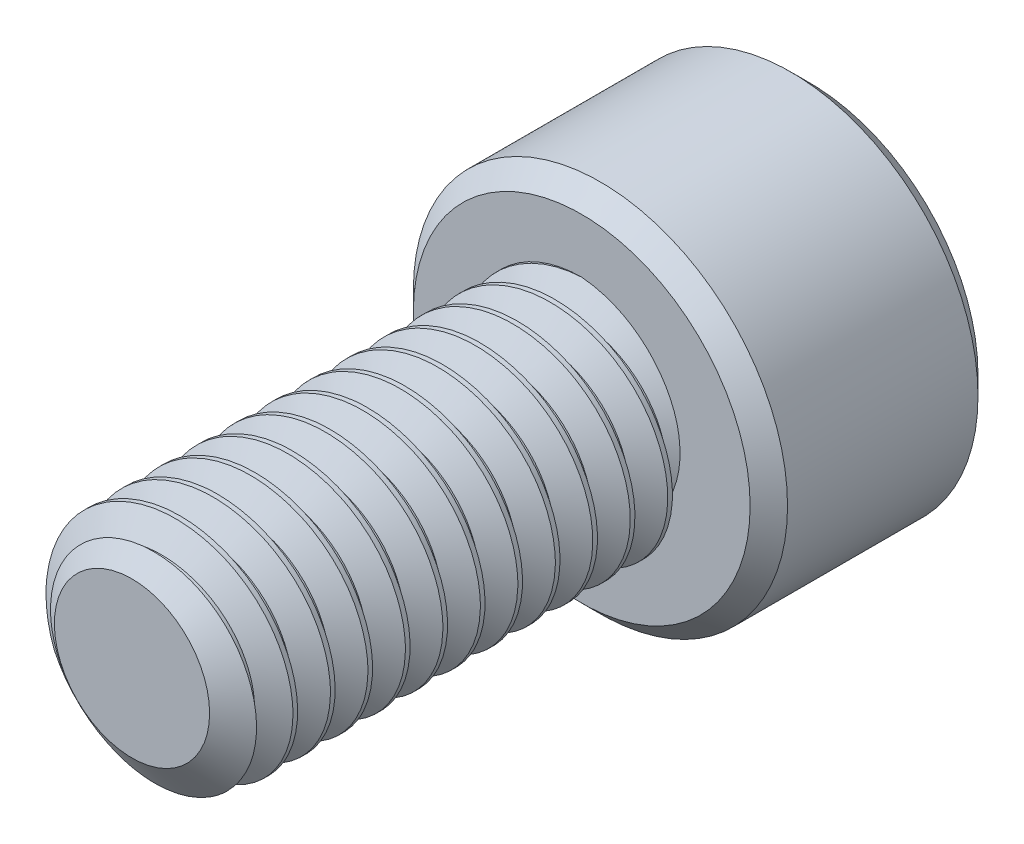
SolidWorks part; units mm, degrees
note: '?' marks a value the reader was unsure of.
other "DetailItem1"
material "Nylon 6/10"
ref_plane "Front Plane" through (0, 0, 0) normal (0, 0, 1) x (1, 0, 0)
ref_plane "Top Plane" through (0, 0, 0) normal (0, 1, 0) x (1, 0, 0)
ref_plane "Right Plane" through (0, 0, 0) normal (1, 0, 0) x (0, 0, -1)
sketch "Sketch1" plane through (0, 0, 0) normal (0, 0, 1) x (1, 0, 0)
  circle A0 centre (0, 0) radius 2.413
  dimension "OD" = 4.826
extrude "Extrude1" add sketch "Sketch1" against normal blind 9.525
sketch "Sketch2" plane through (0, 0, 0) normal (0, 0, 1) x (1, 0, 0)
  circle A0 centre (0, 0) radius 2.413 construction
  circle A1 centre (0, 0) radius 2.413
curve "Helix/Spiral1" pitch 0.7937 height 10.3187 turns 13 parameters "pitch"=0.7937
sketch "Sketch3" plane through (0, 0, 0) normal (1, 0, 0) x (0, 0, -1)
  line L0 (-0.6945, 2.413) -> (-0.3969, 1.8974)
  line L1 (-0.3969, 1.8974) -> (-0.2977, 1.8974)
  line L2 (-0.2977, 1.8974) -> (0, 2.413)
  line L3 (-0.6945, 2.413) -> (0, 2.413)
  line L4 (-0.3473, 2.413) -> (-0.3473, 1.8974) construction
  line L5 (-0.5457, 2.1552) -> (-0.1488, 2.1552) construction
  line L6 (0, 2.413) -> (0, -2.413) construction
  dimension "D1" = 0.0992
  dimension "D2" = 0.3969
  dimension "D3" = 60
sweep "Cut-Sweep1" cut profiles "Sketch3" path "Helix/Spiral1"
sketch "Sketch4" plane through (0, 0, 0) normal (1, 0, 0) x (0, 0, -1)
  line L0 (0.5388, 2.413) -> (0, 1.6434)
  line L1 (0, 1.6434) -> (0, 2.413)
  line L2 (0.5388, 2.413) -> (0, 2.413)
  line L3 (-0.6945, 2.413) -> (0, 2.413) construction
  line L4 (0, 0) -> (7.0209, 0) construction
  dimension "D1" = 55
  dimension "D2" = 0.254
revolve "Cut-Revolve1" cut sketch "Sketch4" angle 360 about L4
sketch "Sketch6" plane through (0, 0, -9.525) normal (0, 0, -1) x (-1, 0, 0)
  circle A0 centre (0, 0) radius 3.9624
  dimension "head dia" = 7.9248
extrude "Extrude2" add sketch "Sketch6" along normal blind 4.826
sketch "Sketch7" plane through (0, 0, -14.351) normal (0, 0, -1) x (-1, 0, 0)
  line L1 (0, 2.2914) -> (-1.9844, 1.1457)
  line L2 (-1.9844, 1.1457) -> (-1.9844, -1.1457)
  line L3 (-1.9844, -1.1457) -> (0, -2.2914)
  line L4 (0, -2.2914) -> (1.9844, -1.1457)
  line L5 (1.9844, -1.1457) -> (1.9844, 1.1457)
  line L6 (1.9844, 1.1457) -> (0, 2.2914)
  circle A0 centre (0, 0) radius 1.9844 construction
  dimension "hex dia" = 3.9688
extrude "Cut-Extrude1" cut sketch "Sketch7" against normal blind 2.9766
sketch "Sketch8" plane through (0, 0, -14.351) normal (0, 0, -1) x (-1, 0, 0)
  circle A0 centre (0, 0) radius 2.2914
extrude "Cut-Extrude2" cut sketch "Sketch8" against normal through all draft 45
chamfer "Chamfer1" distance 0.3962 angle 45 2 edges at (-3.9624, 0, -14.351) (-3.9624, 0, -9.525)
sketch "Sketch10" plane through (0, 0, -9.525) normal (0, 0, 1) x (1, 0, 0)
  circle A1 centre (0, 0) radius 2.413
  circle A2 centre (0, 0) radius 2.413
  dimension "D1" = 0
ref_plane "Plane1" through (0, 0, -38.1) normal (0, 0, 1) x (1, 0, 0)
extrude "partial thread" [suppressed] add sketch "Sketch10" along normal up to surface (12.7 mm away) separate body
chamfer "Chamfer2" [suppressed] distance 0.0965 angle 45
combine bodies "Combine1" [suppressed] operation type? add bodies to combine 107 108
sketch "Sketch9" plane through (0, 0, 0) normal (1, 0, 0) x (0, 0, -1)
  line L0 (0, 2.413) -> (0, -2.413) construction
  line L1 (1.9844, 2.413) -> (1.9844, -2.413) construction
  dimension "D1" = 1.9844
equation "\"D3@Helix/Spiral1\" = \"screw length@Extrude1\"+\"pitch@Helix/Spiral1\""
equation "\"D1@Sketch3\" = \"pitch@Helix/Spiral1\"*.125"
equation "\"D2@Sketch3\" = \"pitch@Helix/Spiral1\"*.5"
equation "\"D1@Cut-Extrude1\" = \"hex dia@Sketch7\"*.75"
equation "\"D1@Chamfer1\" = \"head dia@Sketch6\"*.05"
equation "\"D1@Sketch9\" = \"pitch@Helix/Spiral1\"*2.5"
equation "\"D1@Chamfer2\"=\"OD@Sketch1\"*.02"
